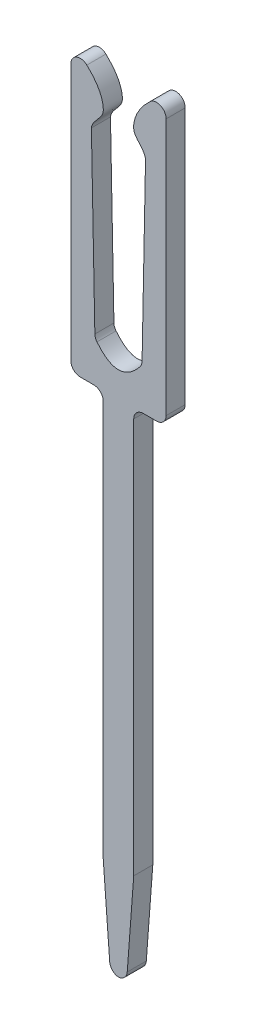
SolidWorks part; units mm, degrees
ref_plane "Ön Düzlem" through (0, 0, 0) normal (0, 0, 1) x (1, 0, 0)
ref_plane "Üst Düzlem" through (0, 0, 0) normal (0, 1, 0) x (1, 0, 0)
ref_plane "Sağ Düzlem" through (0, 0, 0) normal (1, 0, 0) x (0, 0, -1)
sketch "Sketch1" plane through (0, 0, 0) normal (0, 0, 1) x (1, 0, 0)
  line L1 (-56.0817, 40.9171) -> (-55.4017, 40.9171)
  line L2 (-57.4017, 46.9171) -> (-57.4017, 40.9171)
  line L3 (-57.4017, 40.9171) -> (-56.7217, 40.9171)
  line L4 (-55.4017, 46.9171) -> (-55.4017, 40.9171)
  line L5 (-55.8341, 45.5587) -> (-55.9078, 41.7863)
  line L6 (-56.7217, 40.9171) -> (-56.7217, 30.4171)
  line L7 (-56.7217, 30.4171) -> (-56.0817, 30.4171)
  line L8 (-56.0817, 40.9171) -> (-56.0817, 30.4171)
  line L9 (-56.9694, 45.5587) -> (-56.8957, 41.7863)
  spline S0 degree 3 poles (-55.4017, 46.9171) (-55.6865, 46.7243) (-56.0703, 46.4117) (-56.0911, 45.8386) (-55.8533, 45.7263) (-55.8341, 45.5587) knots 0 0 0 0 0.663172 0.707067 1 1 1 1
  spline S1 degree 3 poles (-57.4017, 46.9171) (-57.1169, 46.7243) (-56.7332, 46.4117) (-56.7124, 45.8386) (-56.9502, 45.7263) (-56.9694, 45.5587) knots 0 0 0 0 0.663172 0.707067 1 1 1 1
  spline S2 degree 2 poles (-56.8957, 41.7863) (-56.4017, 41.1144) (-55.9078, 41.7863) knots 0 0 0 1 1 1
  dimension "D1" = 2
  dimension "D2" = 6
  dimension "D3" = 0.64
  dimension "D4" = 0.68
  dimension "D5" = 10.5
extrude "Boss-Extrude1" add sketch "Sketch1" along normal blind 0.4 contours S2 L5 S0 L4 L1 L8 L7 L6 L3 L2 S1 L9
chamfer "Chamfer1" distance 0.15 distance2 2 2 edges at (-56.7217, 30.4171, 0.2) (-56.0817, 30.4171, 0.2) first distance on face at (-56.4017, 30.4171, 0.2)
fillet "Fillet1" radius 0.2 10 edges at (-56.5717, 30.4171, 0.2) (-56.2317, 30.4171, 0.2) (-57.4017, 46.9171, 0.2) (-55.4017, 46.9171, 0.2) (-56.8957, 41.7863, 0.2) (-55.9078, 41.7863, 0.2) (-56.0817, 40.9171, 0.2) (-56.7217, 40.9171, 0.2) (-57.4017, 40.9171, 0.2) (-55.4017, 40.9171, 0.2)
